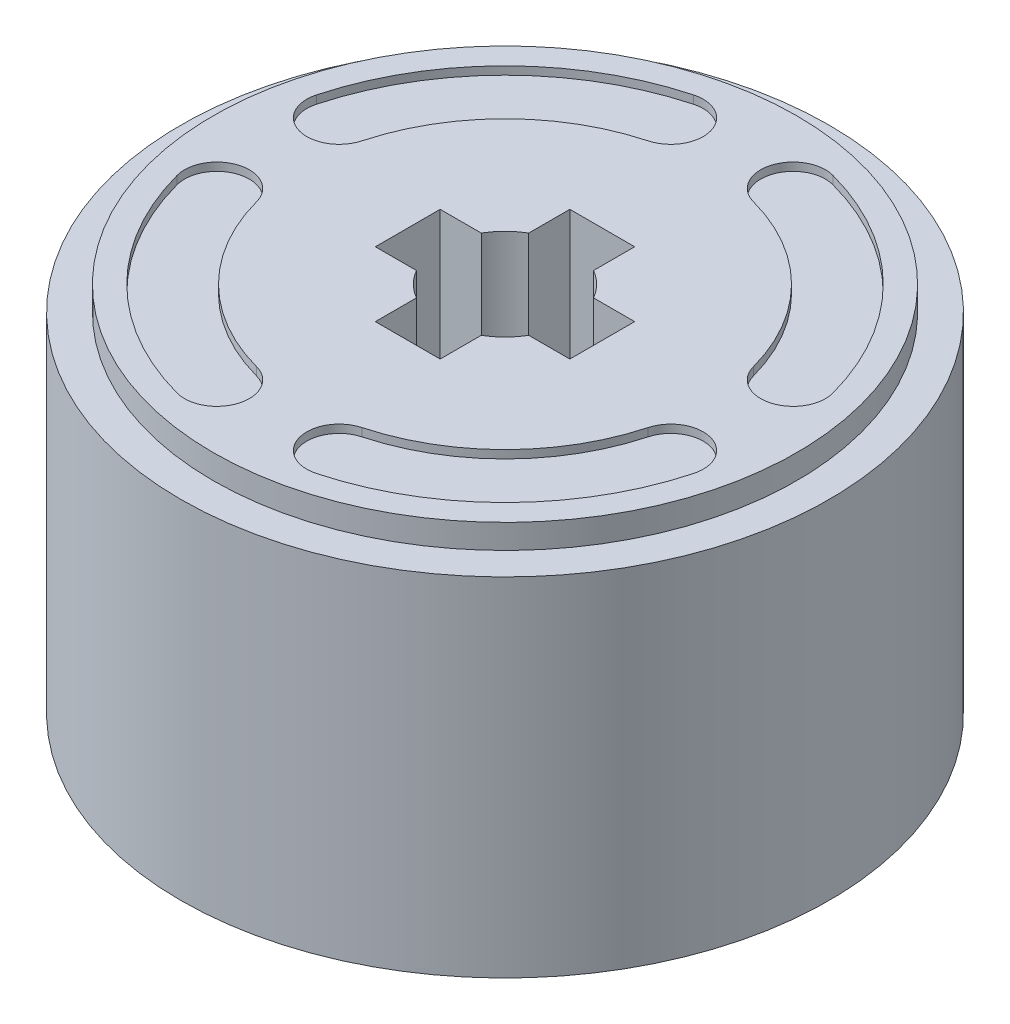
SolidWorks part; units mm, degrees
material "1060 Alloy"
ref_plane "Front Plane" through (0, 0, 0) normal (0, 0, 1) x (1, 0, 0)
ref_plane "Top Plane" through (0, 0, 0) normal (0, 1, 0) x (1, 0, 0)
ref_plane "Right Plane" through (0, 0, 0) normal (1, 0, 0) x (0, 0, -1)
sketch "Sketch1" plane through (0, 0, 0) normal (0, 1, 0) x (1, 0, 0)
  line L0 (-1.4, 4.2) -> (-1.4, 2.4249)
  line L1 (-2.4249, 1.4) -> (-4.2, 1.4)
  line L2 (-4.2, 1.4) -> (-4.2, -1.4)
  line L3 (-4.2, -1.4) -> (-2.4249, -1.4)
  line L4 (-1.4, -2.4249) -> (-1.4, -4.2)
  line L5 (-1.4, -4.2) -> (1.4, -4.2)
  line L6 (1.4, -4.2) -> (1.4, -2.4249)
  line L7 (2.4249, -1.4) -> (4.2, -1.4)
  line L8 (4.2, -1.4) -> (4.2, 1.4)
  line L9 (4.2, 1.4) -> (2.4249, 1.4)
  line L10 (1.4, 2.4249) -> (1.4, 4.2)
  line L11 (1.4, 4.2) -> (-1.4, 4.2)
  line L12 (0, 4.2) -> (0, -4.2) construction
  line L13 (4.2, 0) -> (-4.2, 0) construction
  circle A0 centre (0, 0) radius 14
  arc A1 (-2.4249, -1.4) -> (-1.4, -2.4249) centre (0, 0) ccw
  arc A2 (-1.4, 2.4249) -> (-2.4249, 1.4) centre (0, 0) ccw
  arc A3 (2.4249, 1.4) -> (1.4, 2.4249) centre (0, 0) ccw
  arc A4 (1.4, -2.4249) -> (2.4249, -1.4) centre (0, 0) ccw
  point P23 (0, 0)
  dimension "D1" = 28
  dimension "D8" = 5.6
  dimension "D2" = 8.4
  dimension "D3" = 8.4
  dimension "D4" = 2.8
  dimension "D5" = 2.8
  dimension "D6" = 2.8
  dimension "D7" = 2.8
extrude "Boss-Extrude2" add sketch "Sketch1" along normal blind 16.05
sketch "Sketch3" plane through (0, 16.05, 0) normal (0, 1, 0) x (1, 0, 0)
  line L0 (0, 0) -> (14, 0) construction
  line L1 (0, 0) -> (9.8995, 9.8995) construction
  line L2 (0, 0) -> (9.8995, -9.8995) construction
  line L3 (0, 0) -> (-9.8995, -9.8995) construction
  line L4 (0, 0) -> (-9.8995, 9.8995) construction
  circle A0 centre (0, 0) radius 12.6
  arc A1 (9.8005, 2.6406) -> (2.6406, 9.8005) centre (0, 0) ccw construction
  arc A2 (11.1523, 3.0048) -> (3.0048, 11.1523) centre (0, 0) ccw
  arc A3 (8.4487, 2.2764) -> (2.2764, 8.4487) centre (0, 0) ccw
  arc A4 (8.4487, 2.2764) -> (11.1523, 3.0048) centre (9.8005, 2.6406) ccw
  arc A5 (3.0048, 11.1523) -> (2.2764, 8.4487) centre (2.6406, 9.8005) ccw
  circle A6 centre (0, 0) radius 14 construction
  arc A7 (2.6406, -9.8005) -> (9.8005, -2.6406) centre (0, 0) ccw construction
  arc A8 (3.0048, -11.1523) -> (11.1523, -3.0048) centre (0, 0) ccw
  arc A9 (2.2764, -8.4487) -> (8.4487, -2.2764) centre (0, 0) ccw
  arc A10 (2.2764, -8.4487) -> (3.0048, -11.1523) centre (2.6406, -9.8005) ccw
  arc A11 (11.1523, -3.0048) -> (8.4487, -2.2764) centre (9.8005, -2.6406) ccw
  arc A12 (-9.8005, -2.6406) -> (-2.6406, -9.8005) centre (0, 0) ccw construction
  arc A13 (-11.1523, -3.0048) -> (-3.0048, -11.1523) centre (0, 0) ccw
  arc A14 (-8.4487, -2.2764) -> (-2.2764, -8.4487) centre (0, 0) ccw
  arc A15 (-8.4487, -2.2764) -> (-11.1523, -3.0048) centre (-9.8005, -2.6406) ccw
  arc A16 (-3.0048, -11.1523) -> (-2.2764, -8.4487) centre (-2.6406, -9.8005) ccw
  arc A17 (-2.6406, 9.8005) -> (-9.8005, 2.6406) centre (0, 0) ccw construction
  arc A18 (-3.0048, 11.1523) -> (-11.1523, 3.0048) centre (0, 0) ccw
  arc A19 (-2.2764, 8.4487) -> (-8.4487, 2.2764) centre (0, 0) ccw
  arc A20 (-2.2764, 8.4487) -> (-3.0048, 11.1523) centre (-2.6406, 9.8005) ccw
  arc A21 (-11.1523, 3.0048) -> (-8.4487, 2.2764) centre (-9.8005, 2.6406) ccw
  circle A22 centre (0, 0) radius 14
  point P5 (7.1771, 7.1771)
  point P21 (7.1771, -7.1771)
  point P29 (-7.1771, -7.1771)
  point P37 (-7.1771, 7.1771)
  point P43 (0, 0)
  circle M9 centre (0, 0) radius 14
  dimension "D1" = 25.2
  dimension "D2" = 11.55
  dimension "D3" = 8.75
  dimension "D4" = 8.729
  dimension "D5" = 45
  dimension "D6" = 4
extrude "Cut-Extrude1" cut sketch "Sketch3" against normal blind 1.05 contours A0 M9 region at (-13.604, 16.05, 0)
extrude "Cut-Extrude2" cut sketch "Sketch3<3>" against normal blind 0.35 contours A18 A21 A19 A20 | A13 A16 A14 A15 | A8 A11 A9 A10 | A2 A5 A3 A4 region at (6.7463, 16.05, -6.7463) region at (6.7463, 16.05, 6.7463) region at (-6.7463, 16.05, 6.7463) region at (-6.7463, 16.05, -6.7463)
sketch "Sketch3<3>" plane through (0, 16.05, 0) normal (0, 1, 0) x (1, 0, 0) same geometry as "Sketch3"
